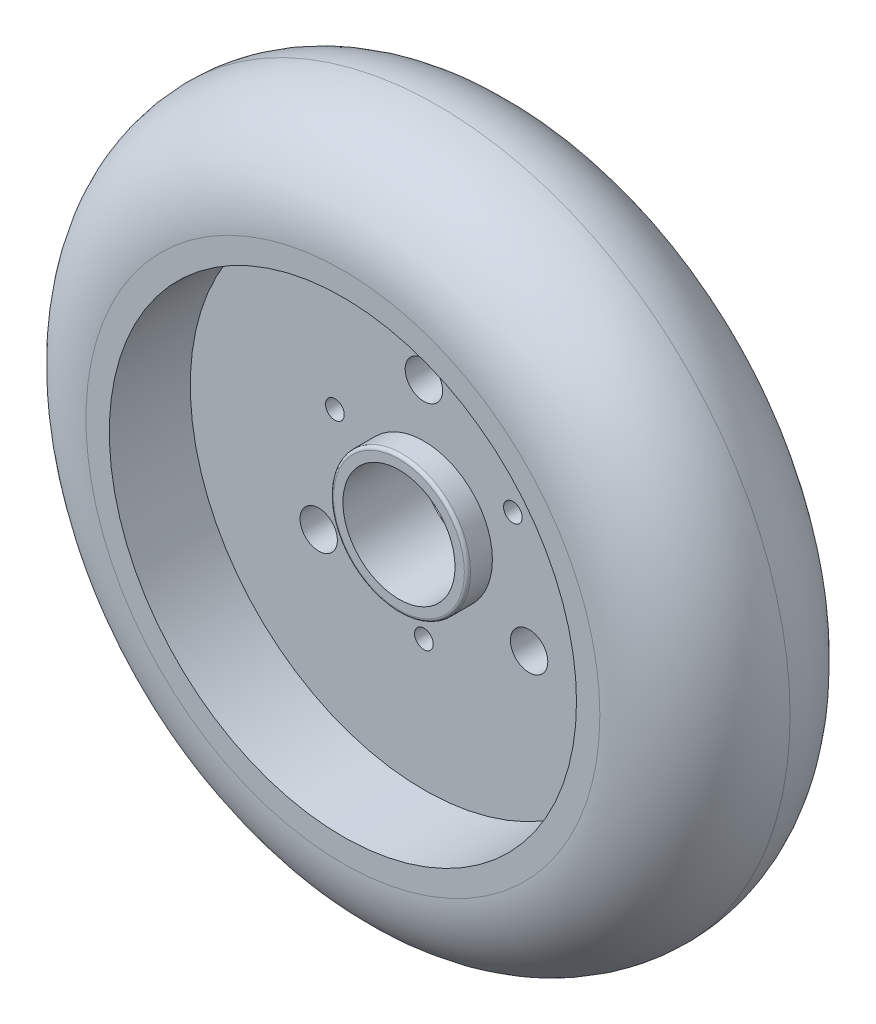
SolidWorks part; units mm, degrees
material "ABS"
ref_plane "Front Plane" through (0, 0, 0) normal (0, 0, 1) x (1, 0, 0)
ref_plane "Top Plane" through (0, 0, 0) normal (0, 1, 0) x (1, 0, 0)
ref_plane "Right Plane" through (0, 0, 0) normal (1, 0, 0) x (0, 0, -1)
sketch "Sketch1" plane through (0, 0, 0) normal (0, 0, 1) x (1, 0, 0)
  circle A0 centre (0, 0) radius 28.7083
extrude "Boss-Extrude1" add sketch "Sketch1" along normal blind 15.5092
fillet "Fillet1" radius 7.7546 2 edges at (28.7083, 0, 0) (28.7083, 0, 15.5092)
sketch "Sketch2" plane through (0, 0, 15.5092) normal (0, 0, 1) x (1, 0, 0)
  circle A0 centre (0, 0) radius 19.05
extrude "Cut-Extrude2" cut sketch "Sketch2" against normal blind 6.604
sketch "Sketch3" plane through (0, 0, 0) normal (0, 0, -1) x (-1, 0, 0)
  circle A0 centre (0, 0) radius 19.05
extrude "Cut-Extrude3" cut sketch "Sketch3" against normal blind 6.604
sketch "Sketch4" plane through (0, 0, 8.9052) normal (0, 0, 1) x (1, 0, 0)
  circle A0 centre (0, 0) radius 5.588
  circle A1 centre (0, 0) radius 4.572
  dimension "D1" = 1.016
extrude "Boss-Extrude2" add sketch "Sketch4" along normal blind 2.032
sketch "Sketch5" plane through (0, 0, 8.9052) normal (0, 0, 1) x (1, 0, 0)
  circle A0 centre (0, 0) radius 4.572
extrude "Cut-Extrude4" cut sketch "Sketch5" against normal blind 11.43
ref_plane "Plane4" through (0, 0, 7.7546) normal (0, 0, 1) x (1, 0, 0)
mirror "Mirror4" about plane through (0, 0, 7.7546) normal (0, 0, 1) of "Boss-Extrude2"
sketch "Sketch6" plane through (0, 0, 8.9052) normal (0, 0, 1) x (1, 0, 0)
  line L0 (0, 4.572) -> (0, 9.906) construction
  line L1 (0, -8.5301) -> (0, 8.5301) construction
  circle A0 centre (0, 0) radius 4.572 construction
  circle A1 centre (0, 9.906) radius 1.524
extrude "Cut-Extrude5" cut sketch "Sketch6" against normal blind 11.43
pattern_circular "CirPattern1" count 3 every 120 about axis through (0, 0, 10.9372) along (0, 0, 1) of "Cut-Extrude5"
sketch "Sketch10" plane through (0, 0, 8.9052) normal (0, 0, 1) x (1, 0, 0)
  line L0 (0, -4.572) -> (0, -8.382) construction
  line L1 (0, -8.5301) -> (0, 8.5301) construction
  circle A0 centre (0, 0) radius 4.572 construction
  circle A1 centre (0, -8.382) radius 0.762
extrude "Cut-Extrude8" cut sketch "Sketch10" against normal blind 11.43
pattern_circular "CirPattern3" count 3 every 120 about axis through (0, 0, 10.9372) along (0, 0, 1) of "Cut-Extrude8"
fillet "Fillet2" radius 0.254 1 edges at (5.588, 0, 10.9372)
fillet "Fillet3" radius 0.254 1 edges at (5.588, 0, 4.572)
ref_point "Point4"
ref_point "Point5"
